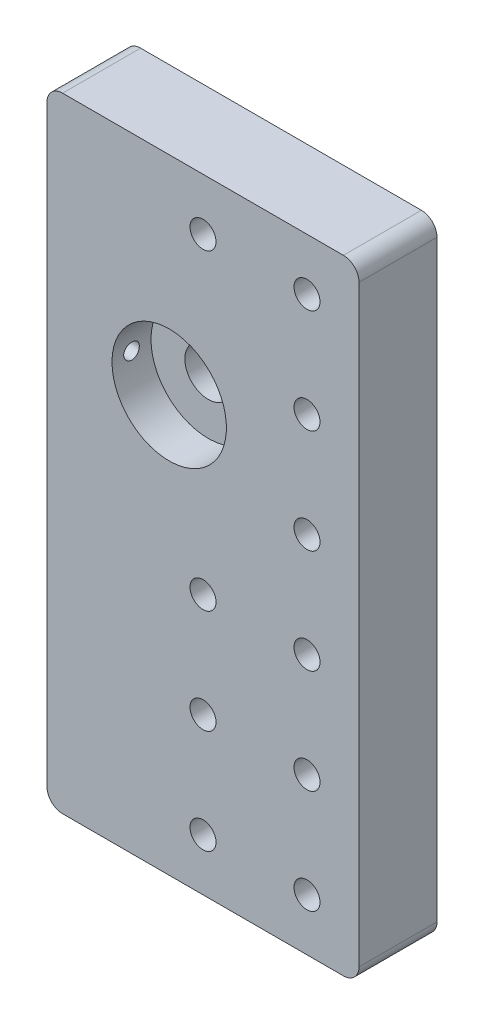
SolidWorks part; units mm, degrees
ref_plane "Płaszczyzna przednia" through (0, 0, 0) normal (0, 0, 1) x (1, 0, 0)
ref_plane "Płaszczyzna górna" through (0, 0, 0) normal (0, 1, 0) x (1, 0, 0)
ref_plane "Płaszczyzna prawa" through (0, 0, 0) normal (1, 0, 0) x (0, 0, -1)
sketch "Sketch1" plane through (0, 0, 0) normal (0, 0, 1) x (1, 0, 0)
  line L0 (72.0964, 110) -> (-17.7275, 110) construction
  line L1 (0, 0) -> (60, 0)
  line L2 (0, 0) -> (0, 120)
  line L3 (0, 120) -> (60, 120)
  line L4 (60, 0) -> (60, 120)
  line L5 (10, 111.3456) -> (10, -27.1164) construction
  line L6 (-17.7275, 10) -> (75.4304, 10) construction
  line L7 (-17.7275, 50) -> (77.7275, 50) construction
  circle A0 centre (10, 110) radius 2.5
  circle A1 centre (30, 110) radius 2.5
  circle A2 centre (10, 90) radius 2.5
  circle A3 centre (10, 70) radius 2.5
  circle A5 centre (10, 10) radius 2.5
  circle A6 centre (30, 10) radius 2.5
  circle A8 centre (30, 50) radius 2.5
  circle A9 centre (10, 50) radius 2.5
  circle A10 centre (10, 30) radius 2.5
  circle A11 centre (30, 30) radius 2.5
  dimension "D11" = 5
  dimension "D1" = 120
  dimension "D2" = 60
  dimension "D3" = 10
  dimension "D4" = 10
  dimension "D5" = 10
  dimension "D6" = 20
  dimension "D7" = 20
  dimension "D8" = 20
  dimension "D9" = 20
  dimension "D10" = 20
  dimension "D12" = 20
extrude "Boss-Extrude1" add sketch "Sketch1" along normal blind 15
fillet "Fillet1" radius 3 4 edges at (0, 0, 7.5) (60, 0, 7.5) (0, 120, 7.5) (60, 120, 7.5)
sketch "Sketch2" plane through (0, 0, 15) normal (0, 0, 1) x (1, 0, 0)
  line L0 (45.9963, 120) -> (36.5, 120) construction
  line L1 (57, 120) -> (3, 120) construction
  line L2 (36.5, 120) -> (36.5, 0) construction
  line L3 (3, 0) -> (57, 0) construction
  line L4 (0, 117) -> (0, 3) construction
  line L5 (0, 80) -> (60, 80) construction
  line L6 (60, 3) -> (60, 117) construction
  circle A0 centre (10, 70) radius 2.5 construction
  circle A1 centre (10, 90) radius 2.5 construction
  circle A2 centre (36.5, 80) radius 11
  circle A7 centre (36.5, 80) radius 4.5
  dimension "D5" = 22
  dimension "D6" = 9
  dimension "D1" = 36.5
extrude "Cut-Extrude1" cut sketch "Sketch2" against normal through all contours A7
extrude "Cut-Extrude2" cut sketch "Sketch2<3>" against normal blind 7.5 contours A2 A7 region at (25.8111, 80, 15)
sketch "Sketch2<3>" plane through (0, 0, 15) normal (0, 0, 1) x (1, 0, 0) same geometry as "Sketch2"
mirror "Mirror1" about plane through (60, 0, 15) normal (-1, 0, 0) of bodies 103
delete or keep bodies "Body-Delete/Keep 1" type delete bodies bodies 103
sketch "Sketch3" plane through (60, 0, 0) normal (-1, 0, 0) x (0, 0, 1)
  line L0 (15, 80) -> (7.5, 80) construction
  line L1 (15, 3) -> (15, 117) construction
  line L2 (15, 69) -> (15, 91) construction
  line L3 (7.5, 69) -> (7.5, 91) construction
  circle A0 centre (11.25, 80) radius 1.5
  dimension "D1" = 3
extrude "Cut-Extrude3" cut sketch "Sketch3" against normal up to next
